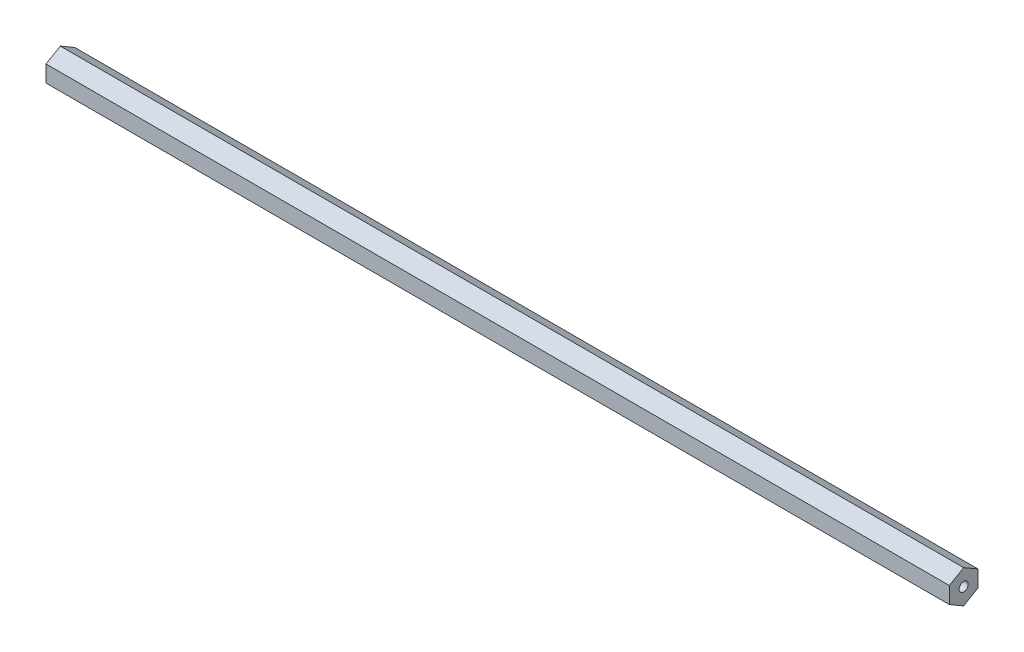
SolidWorks part; units mm, degrees
material "7075-T6 (SN)"
ref_plane "Front Plane" through (0, 0, 0) normal (0, 0, 1) x (1, 0, 0)
ref_plane "Top Plane" through (0, 0, 0) normal (0, 1, 0) x (1, 0, 0)
ref_plane "Right Plane" through (0, 0, 0) normal (1, 0, 0) x (0, 0, -1)
sketch "Sketch1" plane through (0, 0, 0) normal (1, 0, 0) x (0, 0, -1)
  line L1 (0, 7.3323) -> (-6.35, 3.6662)
  line L2 (-6.35, 3.6662) -> (-6.35, -3.6662)
  line L3 (-6.35, -3.6662) -> (0, -7.3323)
  line L4 (0, -7.3323) -> (6.35, -3.6662)
  line L5 (6.35, -3.6662) -> (6.35, 3.6662)
  line L6 (6.35, 3.6662) -> (0, 7.3323)
  circle A2 centre (0, 0) radius 6.35 construction
  dimension "D2" = 12.7
extrude "Boss-Extrude1" add sketch "Sketch1" along normal mid plane 400.05 contours L5 L6 L1 L2 L3 L4 region at (0, 0, 0)
sketch "Sketch3" plane through (-200.025, 0, 0) normal (-1, 0, 0) x (0, 0, 1)
  circle A0 centre (0, 0) radius 6.35
  dimension "D1" = 12.7
hole_wizard "#10-32 Tapped Hole1" positions "3DSketch1" profile "Sketch4" tap size "#10-32" standard "ANSI Inch"
sketch3d "3DSketch1"
  point P10 (200.025, 0, 0)
  point P13 (-200.025, 0, 0)
sketch "Sketch4" plane through (200.025, 0, 0) normal (0, 1, 0) x (0, 0, -1)
  line L0 (0, 0) -> (0, 17.5608)
  line L1 (0, 17.5608) -> (2.0193, 16.3474)
  line L2 (2.0193, 16.3474) -> (2.0193, 0)
  line L5 (2.0193, 0) -> (0, 0)
  line L10 (0, 17.5608) -> (-2.0193, 16.3474) construction
  line L11 (0, -6.35) -> (0, 107.95) construction
  dimension "Tap Drill Dia." = 4.0386
  dimension "Tap Drill Depth" = 16.3474
  dimension "Drill Angle" = 118
cosmetic thread "Hole Thread1" parameters "D1"=13.97, "D2"=4.826
cosmetic thread "Hole Thread2" parameters "D1"=13.97, "D2"=4.826
